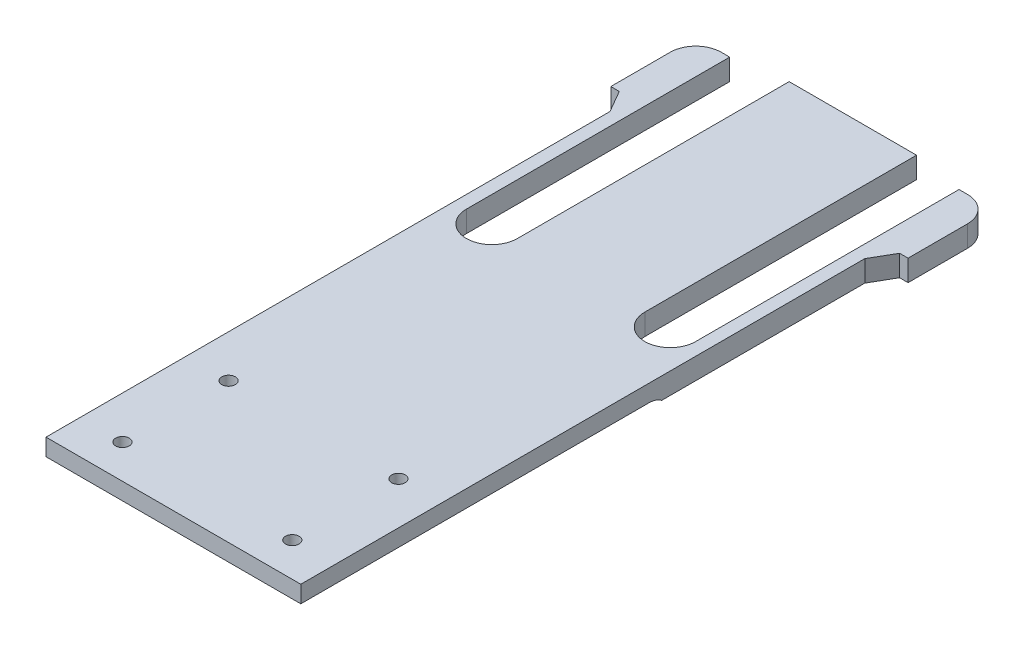
SolidWorks part; units mm, degrees
material "PLA"
ref_plane "Front Plane" through (0, 0, 0) normal (0, 0, 1) x (1, 0, 0)
ref_plane "Top Plane" through (0, 0, 0) normal (0, 1, 0) x (1, 0, 0)
ref_plane "Right Plane" through (0, 0, 0) normal (1, 0, 0) x (0, 0, -1)
sketch "Sketch2" plane through (0, 0, 0) normal (0, 1, 0) x (1, 0, 0)
  line L0 (0, 0) -> (0, -160) construction
  line L5 (15, 0) -> (-15, 0)
  line L13 (-15, 0) -> (-15, -70)
  line L14 (-15, -70) -> (-27, -70)
  line L15 (-27, -70) -> (-27, -2)
  line L16 (-27, -2) -> (-35, -2)
  line L17 (-35, -2) -> (-35, -22)
  line L18 (-35, -22) -> (-30, -22)
  line L19 (-30, -22) -> (-30, -160)
  line L20 (-30, -160) -> (30, -160)
  line L21 (30, -22) -> (30, -160)
  line L22 (35, -22) -> (30, -22)
  line L23 (35, -2) -> (35, -22)
  line L24 (27, -2) -> (35, -2)
  line L25 (27, -70) -> (27, -2)
  line L26 (15, -70) -> (27, -70)
  line L27 (15, 0) -> (15, -70)
  dimension "D1" = 160
  dimension "D2" = 30
  dimension "D3" = 2
  dimension "D4" = 20
  dimension "D5" = 3
  dimension "D6" = 5
  dimension "D7" = 15
  dimension "D8" = 90
extrude "Boss-Extrude1" add sketch "Sketch2" along normal blind 5
fillet "Fillet1" radius 6 6 edges at (-27, 2.5, 70) (-15, 2.5, 70) (15, 2.5, 70) (27, 2.5, 70) (-35, 2.5, 2) (35, 2.5, 2)
chamfer "Chamfer1" distance 3 angle 60 1 edges at (-30, 2.5, 22) first distance on face at (-32.5, 2.5, 22)
chamfer "Chamfer2" distance 3 angle 60 1 edges at (30, 2.5, 22) first distance on face at (32.5, 2.5, 22)
sketch "Sketch4" plane through (0, 5, 0) normal (0, 1, 0) x (1, 0, 0)
  line L0 (-30, -152) -> (30, -152) construction
  line L1 (-30, -27.1962) -> (-30, -160) construction
  line L2 (30, -160) -> (30, -27.1962) construction
  line L3 (0, -160) -> (0, -107.1676) construction
  line L4 (-30, -160) -> (30, -160) construction
  circle A0 centre (-20, -152) radius 1.6
  circle A3 centre (20, -152) radius 1.6
  circle A4 centre (-20, -127) radius 1.6
  circle A5 centre (20, -127) radius 1.6
  dimension "D1" = 3.2
  dimension "D2" = 10
  dimension "D3" = 2
  dimension "D4" = 8
extrude "Cut-Extrude1" cut sketch "Sketch4" against normal up to next
sketch "Sketch5" plane through (-30, 0, 0) normal (-1, 0, 0) x (0, 0, 1)
  line L1 (160, 0) -> (75, 0)
  line L2 (160, 0) -> (160, 1)
  line L3 (160, 1) -> (75, 1)
  line L4 (75, 0) -> (75, 1)
  dimension "D1" = 85
  dimension "D2" = 1
extrude "Cut-Extrude2" cut sketch "Sketch5" against normal up to next
fillet "Fillet3" radius 5 1 edges at (0, 1, 75)
